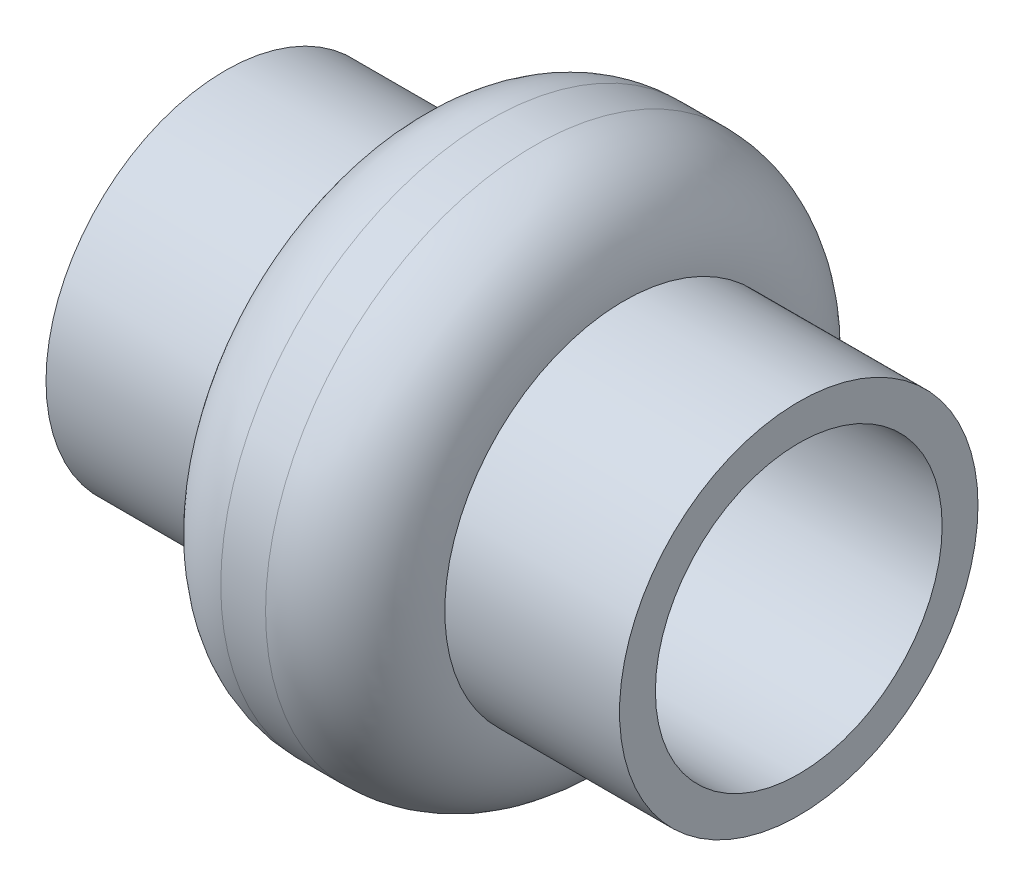
SolidWorks part; units mm, degrees
ref_plane "Top Plane" through (0, 0, 0) normal (0, 0, 1) x (1, 0, 0)
ref_plane "Right Plane" through (0, 0, 0) normal (0, 1, 0) x (1, 0, 0)
ref_plane "Front Plane" through (0, 0, 0) normal (1, 0, 0) x (0, 0, -1)
sketch "Sketch1" plane through (0, 0, 0) normal (1, 0, 0) x (0, 0, -1)
  circle A0 centre (0, 0) radius 3
  dimension "D1" = 6
extrude "Boss-Extrude1" add sketch "Sketch1" along normal mid plane 2.5
sketch "Sketch2" plane through (1.25, 0, 0) normal (1, 0, 0) x (0, 0, -1)
  circle A0 centre (0, 0) radius 2
  dimension "D1" = 4
extrude "Boss-Extrude2" add sketch "Sketch2" along normal offset from surface (1.95 mm away) 3.2 up to plane "Front Plane"
sketch "Sketch3" plane through (-1.25, 0, 0) normal (-1, 0, 0) x (0, 0, 1)
  circle A0 centre (0, 0) radius 2
  circle A1 centre (0, 0) radius 2 construction
extrude "Boss-Extrude8" add sketch "Sketch3" along normal blind 1.95
sketch "Sketch4" plane through (3.2, 0, 0) normal (1, 0, 0) x (0, 0, -1)
  circle A0 centre (0, 0) radius 1.6
  dimension "D1" = 3.2
extrude "Cut-Extrude1" cut sketch "Sketch4" against normal through all
fillet "Fillet1" radius 1 2 edges at (-1.25, 0, -3) (1.25, 0, -3)
